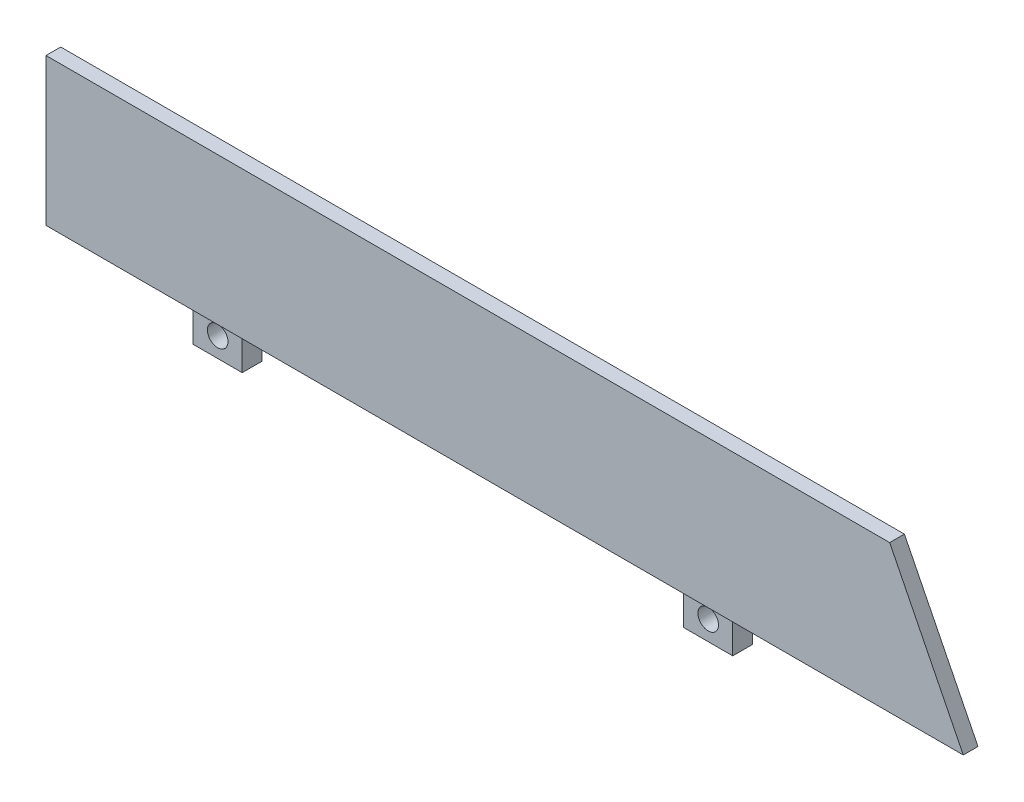
SolidWorks part; units mm, degrees
material "ABS"
ref_plane "Płaszczyzna przednia" through (0, 0, 0) normal (0, 0, 1) x (1, 0, 0)
ref_plane "Płaszczyzna górna" through (0, 0, 0) normal (0, 1, 0) x (1, 0, 0)
ref_plane "Płaszczyzna prawa" through (0, 0, 0) normal (1, 0, 0) x (0, 0, -1)
sketch "Szkic1" plane through (0, 0, 0) normal (0, 0, 1) x (1, 0, 0)
  line L0 (0, 0) -> (187, 0)
  line L1 (0, 0) -> (0, 30)
  line L2 (0, 30) -> (171.9968, 30)
  line L3 (171.9968, 30) -> (187, 0)
  dimension "D1" = 187
  dimension "D2" = 30
  dimension "D3" = 63.43
extrude "Dodanie-wyciągnięcie1" add sketch "Szkic1" along normal blind 3
sketch "Szkic2" plane through (0, 0, 0) normal (0, 0, -1) x (-1, 0, 0)
  line L0 (0, 0) -> (-187, 0) construction
  line L1 (-137, 5) -> (-127, 5)
  line L2 (-137, 5) -> (-137, -9)
  line L3 (-137, -9) -> (-127, -9)
  line L4 (-127, 5) -> (-127, -9)
  line L5 (-37, 5) -> (-37, -9)
  line L6 (-37, 5) -> (-27, 5)
  line L7 (-27, 5) -> (-27, -9)
  line L8 (-37, -9) -> (-27, -9)
  circle A0 centre (-132, -5) radius 2.1
  circle A1 centre (-32, -5) radius 2.1
  dimension "D5" = 4.2
  dimension "D7" = 5
  dimension "D1" = 10
  dimension "D2" = 14
  dimension "D3" = 5
  dimension "D4" = 50
  dimension "D6" = 4
  dimension "D8" = 2
extrude "Dodanie-wyciągnięcie2" add sketch "Szkic2" along normal blind 4
chamfer "Sfazowanie1" distance 4 angle 45 6 edges at (37, 2.5, 0) (32, 5, 0) (27, 2.5, 0) (127, 2.5, 0) (132, 5, 0) (137, 2.5, 0)
